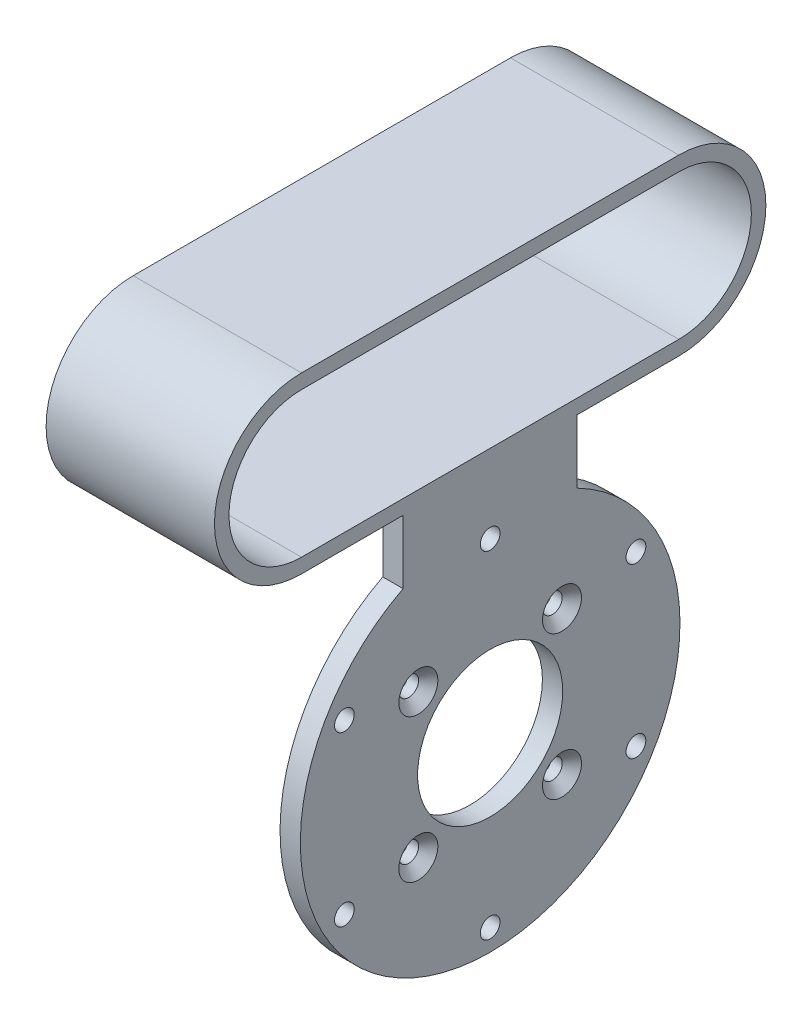
SolidWorks part; units mm, degrees
material "7075-O (SS)"
ref_plane "Front" through (0, 0, 0) normal (0, 0, 1) x (1, 0, 0)
ref_plane "Top" through (0, 0, 0) normal (0, 1, 0) x (1, 0, 0)
ref_plane "Right" through (0, 0, 0) normal (1, 0, 0) x (0, 0, -1)
sketch "Croquis1" plane through (0, 0, 0) normal (1, 0, 0) x (0, 0, -1)
  line L0 (-32.5, 55) -> (32.5, 55) construction
  line L1 (-32.5, 70) -> (32.5, 70) construction
  line L2 (-32.5, 40) -> (32.5, 40) construction
  line L3 (0, 50) -> (0, -50) construction
  line L4 (-15, 40) -> (-15, 29.0567)
  line L5 (15, 40) -> (15, 29.0567)
  line L6 (-32.5, 55) -> (32.5, 55) construction
  line L7 (-32.5, 70) -> (32.5, 70)
  line L9 (-32.5, 40) -> (-15, 40)
  line L10 (32.5, 40) -> (15, 40)
  line L11 (-32.5, 55) -> (32.5, 55) construction
  line L12 (-32.5, 67.5) -> (32.5, 67.5)
  line L13 (-32.5, 42.5) -> (32.5, 42.5)
  arc A0 (-15, 29.0567) -> (15, 29.0567) centre (0, 0) ccw
  circle A1 centre (0, 0) radius 12.5
  arc A2 (-32.5, 70) -> (-32.5, 40) centre (-32.5, 55) ccw construction
  arc A3 (32.5, 40) -> (32.5, 70) centre (32.5, 55) ccw construction
  arc A4 (-32.5, 70) -> (-32.5, 40) centre (-32.5, 55) ccw
  arc A5 (32.5, 40) -> (32.5, 70) centre (32.5, 55) ccw
  arc A6 (-32.5, 67.5) -> (-32.5, 42.5) centre (-32.5, 55) ccw
  arc A7 (32.5, 42.5) -> (32.5, 67.5) centre (32.5, 55) ccw
  point P1 (0, 55)
  point P6 (0, 55)
  point P19 (0, 55)
  dimension "D1" = 65.4
  dimension "D2" = 25
  dimension "D3" = 15
  dimension "D7" = 12.5
  dimension "D4" = 55
  dimension "D5" = 65
  dimension "D6" = 15
extrude "Saliente-Extruir1" add sketch "Croquis1" along normal blind 3.5
hole_wizard "Taladro de margen para M31" positions "Croquis2" profile "Croquis4" hole size "M3" standard "Ansi Metric" end condition up to next
sketch "Croquis2" plane through (3.5, 0, 0) normal (1, 0, 0) x (0, 0, -1)
  line L0 (0, 50) -> (0, -50) construction
  line L1 (50, 0) -> (-50, 0) construction
  point P0 (0, 29)
  point P11 (25.1147, 14.5)
  point P12 (25.1147, -14.5)
  point P13 (0, -29)
  point P14 (-25.1147, -14.5)
  point P15 (-25.1147, 14.5)
  dimension "D1" = 29
  dimension "D3" = 29
  dimension "D2" = 6
sketch "Croquis4" plane through (3.5, 29, 0) normal (0, 1, 0) x (0, 0, -1)
  line L0 (0, 0) -> (0, 3.5)
  line L1 (0, 3.5) -> (1.7, 3.5)
  line L2 (1.7, 3.5) -> (1.7, 0)
  line L5 (1.7, 0) -> (0, 0)
  line L11 (0, -6.35) -> (0, 107.95) construction
  dimension "Diámetro de taladro hasta el siguiente" = 3.4
  dimension "Profundidad de taladro hasta el siguiente" = 3.5
hole_wizard "Refrentado para tornillo tapón con cabeza plana de clavija de M31" positions "Croquis5" profile "Croquis7" countersink size "M3" standard "Ansi Metric" end condition up to next
sketch "Croquis5" plane through (3.5, 0, 0) normal (1, 0, 0) x (0, 0, -1)
  line L1 (-12.3744, -12.3744) -> (12.3744, -12.3744) construction
  line L2 (-12.3744, -12.3744) -> (-12.3744, 12.3744) construction
  line L3 (-12.3744, 12.3744) -> (12.3744, 12.3744) construction
  line L4 (12.3744, -12.3744) -> (12.3744, 12.3744) construction
  line L5 (-12.3744, -12.3744) -> (12.3744, 12.3744) construction
  line L6 (-12.3744, 12.3744) -> (12.3744, -12.3744) construction
  point P2 (12.3744, 12.3744)
  point P29 (-12.3744, -12.3744)
  point P30 (-12.3744, 12.3744)
  point P31 (12.3744, -12.3744)
  dimension "D1" = 35
sketch "Croquis7" plane through (3.5, 12.3744, -12.3744) normal (0, 1, 0) x (0, 0, -1)
  line L0 (0, 0) -> (0, 3.5)
  line L1 (0, 3.5) -> (1.7, 3.5)
  line L2 (1.7, 3.5) -> (1.7, 1.66)
  line L3 (1.7, 1.66) -> (3.36, 0)
  line L5 (3.36, 0) -> (0, 0)
  line L6 (-1.7, 1.66) -> (-3.36, 0) construction
  line L11 (0, -6.35) -> (0, 107.95) construction
  dimension "Diámetro de taladro hasta el siguiente" = 3.4
  dimension "Profundidad de taladro hasta el siguiente" = 3.5
  dimension "Diámetro de avellanado cercano" = 6.72
  dimension "Ángulo de avellanado cercano" = 90
sketch "Croquis8" plane through (3.5, 0, 0) normal (1, 0, 0) x (0, 0, -1)
  line L0 (15, 40) -> (32.5, 40) construction
  line L1 (32.5, 70) -> (-32.5, 70) construction
  line L2 (-32.5, 40) -> (-15, 40) construction
  line L3 (15, 40) -> (32.5, 40)
  line L4 (32.5, 70) -> (-32.5, 70)
  line L5 (-32.5, 40) -> (-15, 40)
  line L6 (15, 40) -> (-15, 40)
  line L7 (-32.5, 55) -> (32.5, 55) construction
  line L8 (-32.5, 67.5) -> (32.5, 67.5)
  line L9 (-32.5, 42.5) -> (32.5, 42.5)
  arc A0 (32.5, 40) -> (32.5, 70) centre (32.5, 55) ccw construction
  arc A1 (-32.5, 70) -> (-32.5, 40) centre (-32.5, 55) ccw construction
  arc A2 (32.5, 40) -> (32.5, 70) centre (32.5, 55) ccw
  arc A3 (-32.5, 70) -> (-32.5, 40) centre (-32.5, 55) ccw
  arc A4 (-32.5, 67.5) -> (-32.5, 42.5) centre (-32.5, 55) ccw
  arc A5 (32.5, 42.5) -> (32.5, 67.5) centre (32.5, 55) ccw
  point P3 (0, 55)
  dimension "D1" = 12.5
extrude "Saliente-Extruir2" add sketch "Croquis8" against normal blind 29
sketch "Croquis12" plane through (-25.5, 0, 0) normal (-1, 0, 0) x (0, 0, 1)
  line L0 (32.5, 42.5) -> (-32.5, 42.5) construction
  line L1 (-32.5, 67.5) -> (32.5, 67.5) construction
  line L2 (32.5, 42.5) -> (-32.5, 42.5)
  line L3 (-32.5, 67.5) -> (32.5, 67.5)
  arc A0 (32.5, 42.5) -> (32.5, 67.5) centre (32.5, 55) ccw construction
  arc A1 (-32.5, 67.5) -> (-32.5, 42.5) centre (-32.5, 55) ccw construction
  arc A2 (32.5, 42.5) -> (32.5, 67.5) centre (32.5, 55) ccw
  arc A3 (-32.5, 67.5) -> (-32.5, 42.5) centre (-32.5, 55) ccw
extrude "Saliente-Extruir3" add sketch "Croquis12" against normal blind 3.5
hole_wizard "Refrentado para tornillo con cabeza troncocónica de M31" positions "Croquis9" profile "Croquis11" counterbore size "M3" standard "Ansi Metric" end condition up to next
sketch "Croquis9" plane through (-25.5, 0, 0) normal (-1, 0, 0) x (0, 0, 1)
  line L0 (-22.5, 55) -> (22.5, 55) construction
  line L3 (0, -50) -> (0, 50) construction
  line L4 (-15, 40) -> (15, 40) construction
  point P0 (-22.5, 55)
  point P1 (22.5, 55)
  point P4 (0, 55)
  dimension "D1" = 45
  dimension "D2" = 15
sketch "Croquis11" plane through (-25.5, 55, -22.5) normal (0, 1, 0) x (0, 0, 1)
  line L0 (0, 0) -> (0, 3.5)
  line L1 (0, 3.5) -> (1.7, 3.5)
  line L3 (1.7, 3.5) -> (1.7, 2.4)
  line L4 (1.7, 2.4) -> (3.5, 2.4)
  line L5 (3.5, 2.4) -> (3.5, 0)
  line L7 (3.5, 0) -> (0, 0)
  line L11 (0, -6.35) -> (0, 107.95) construction
  dimension "Diámetro de taladro hasta el siguiente" = 3.4
  dimension "Profundidad de taladro hasta el siguiente" = 3.5
  dimension "Diámetro de refrentado" = 7
  dimension "Profundidad de refrentado" = 2.4
